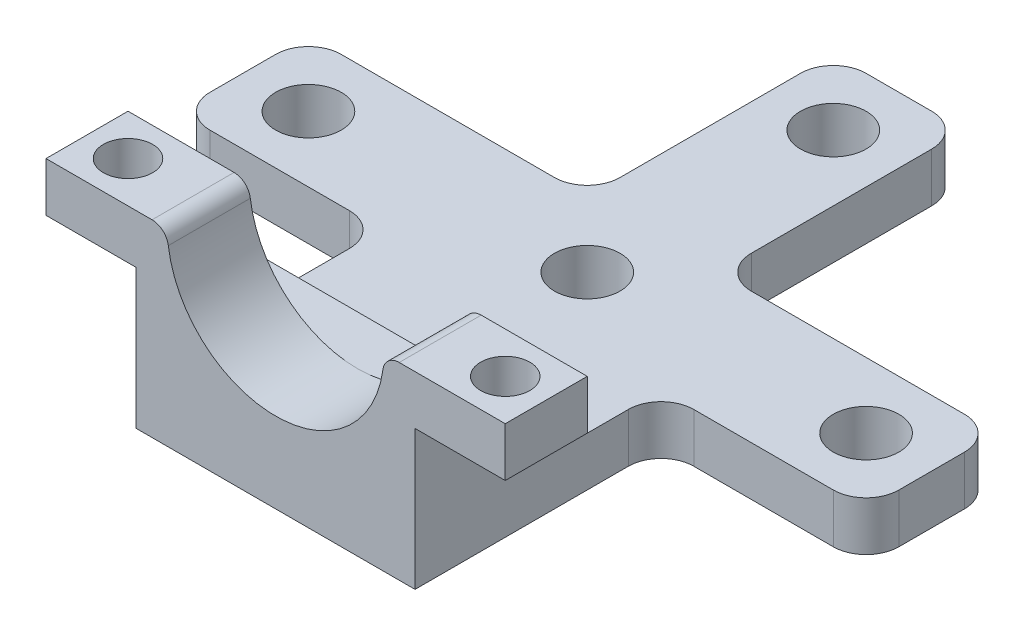
SolidWorks part; units mm, degrees
ref_plane "Front Plane" through (0, 0, 0) normal (0, 0, 1) x (1, 0, 0)
ref_plane "Top Plane" through (0, 0, 0) normal (0, 1, 0) x (1, 0, 0)
ref_plane "Right Plane" through (0, 0, 0) normal (1, 0, 0) x (0, 0, -1)
sketch "Sketch2" plane through (0, 0, 0) normal (0, 1, 0) x (1, 0, 0)
  line L0 (0, 4) -> (0, -4) construction
  line L1 (-21, 4) -> (21, 4)
  line L2 (-21, 4) -> (-21, -4)
  line L3 (-21, -4) -> (21, -4)
  line L4 (21, 4) -> (21, -4)
  line L5 (-21, 4) -> (21, -4) construction
  line L6 (-21, -4) -> (21, 4) construction
  line L7 (-21, 0) -> (21, 0) construction
  line L8 (-4, 4) -> (-4, 19)
  line L9 (-4, 19) -> (4, 19)
  line L10 (4, 19) -> (4, 4)
  line L11 (0, 4) -> (0, 19) construction
  line L12 (-8.5, -4) -> (-8.5, -19)
  line L13 (-8.5, -19) -> (8.5, -19)
  line L14 (8.5, -19) -> (8.5, -4)
  circle A0 centre (0, 0) radius 2
  circle A1 centre (-17, 0) radius 2
  circle A2 centre (17, 0) radius 2
  circle A3 centre (0, 15) radius 2
  point P0 (0, 0)
  dimension "D3" = 4
  dimension "D4" = 4
  dimension "D5" = 17
  dimension "D9" = 4
  dimension "D1" = 42
  dimension "D2" = 8
  dimension "D7" = 15
  dimension "D8" = 8
  dimension "D10" = 15
  dimension "D11" = 15
  dimension "D12" = 17
  dimension "D6" = 3
extrude "Boss-Extrude1" add sketch "Sketch2" along normal blind 3 contours L10 L9 L8 L1 A3 | L4 L1 L2 L3 A2 A1 A0 region at (-12.5, 0, -3.5724) region at (0, 0, -11.0906)
extrude "Boss-Extrude2" add sketch "Sketch2<3>" along normal blind 3 contours L13 L14 L3 L12 region at (0, 0, 11.5)
sketch "Sketch2<3>" plane through (0, 0, 0) normal (0, 1, 0) x (1, 0, 0) same geometry as "Sketch2"
sketch "Sketch3" plane through (0, 0, 19) normal (0, 0, 1) x (1, 0, 0)
  line L0 (0, 0) -> (0, 24.2581) construction
  line L1 (-8.5, 0) -> (8.5, 0) construction
  line L2 (-8.5, 11.5) -> (-14, 11.5)
  line L3 (-8.5, 8.5) -> (-8.5, 3)
  line L4 (-8.5, 3) -> (8.5, 3)
  line L5 (-8.5, 11.5) -> (-6.6, 11.5)
  line L6 (14, 8.5) -> (8.5, 8.5)
  line L7 (-8.5, 3) -> (8.5, 3) construction
  line L8 (-14, 11.5) -> (-14, 8.5)
  line L9 (-14, 8.5) -> (-8.5, 8.5)
  line L10 (14, 11.5) -> (14, 8.5)
  line L11 (8.5, 11.5) -> (6.6, 11.5)
  line L12 (8.5, 8.5) -> (8.5, 3)
  line L13 (8.5, 11.5) -> (14, 11.5)
  arc A1 (-6.6, 11.5) -> (6.6, 11.5) centre (0, 11.5) ccw
  point P20 (0, 3)
  dimension "D1" = 8.5
  dimension "D2" = 13.2
  dimension "D3" = 8.5
  dimension "D5" = 14
  dimension "D6" = 3
extrude "Boss-Extrude3" add sketch "Sketch3" against normal blind 5
sketch "Sketch4" plane through (0, 0, 14) normal (0, 0, -1) x (-1, 0, 0)
  line L0 (8.5, 8.5) -> (8.5, 3) construction
  line L1 (-8.5, 3) -> (8.5, 3)
  line L2 (-8.5, 3) -> (-8.5, 4.9)
  line L3 (-8.5, 4.9) -> (8.5, 4.9)
  line L4 (8.5, 3) -> (8.5, 4.9)
  arc A0 (-6.6, 11.5) -> (6.6, 11.5) centre (0, 11.5) ccw construction
extrude "Boss-Extrude4" add sketch "Sketch4" along normal blind 3
sketch "Sketch5" plane through (0, 8.5, 0) normal (0, -1, 0) x (1, 0, 0)
  line L0 (-14, 16.5) -> (14, 16.5) construction
  line L1 (-14, 14) -> (-14, 19) construction
  line L2 (14, 14) -> (14, 19) construction
  line L3 (0, 19) -> (0, 11.0024) construction
  line L4 (-8.5, 19) -> (8.5, 19) construction
  circle A0 centre (11.5, 16.5) radius 1.5
  circle A1 centre (-11.5, 16.5) radius 1.5
  dimension "D1" = 2.5
  dimension "D2" = 3
extrude "Cut-Extrude1" cut sketch "Sketch5" against normal through all
fillet "Fillet1" radius 1 2 edges at (6.6, 11.5, 16.5) (-6.6, 11.5, 16.5)
fillet "Fillet2" radius 2 10 edges at (-21, 1.5, 4) (-21, 1.5, -4) (-4, 1.5, -19) (4, 1.5, -19) (21, 1.5, -4) (21, 1.5, 4) (4, 1.5, -4) (-4, 1.5, -4) (-8.5, 1.5, 4) (8.5, 1.5, 4)
sketch "Sketch6" plane through (0, 3, 0) normal (0, 1, 0) x (1, 0, 0)
  line L0 (-8.5, -11) -> (8.5, -11) construction
  line L1 (-5.5, -11) -> (5.5, -11)
  line L2 (-5.5, -11) -> (-5.5, -7)
  line L3 (-3.5, -5) -> (3.5, -5)
  line L4 (5.5, -11) -> (5.5, -7)
  line L5 (0, 0) -> (0, -11) construction
  line L6 (-8.5, -6) -> (-8.5, -11) construction
  arc A0 (-5.5, -7) -> (-3.5, -5) centre (-3.5, -7) cw
  arc A1 (3.5, -5) -> (5.5, -7) centre (3.5, -7) cw
  dimension "D3" = 2
  dimension "D1" = 6
  dimension "D2" = 3
extrude "Cut-Extrude2" [suppressed] cut sketch "Sketch6" against normal through all
